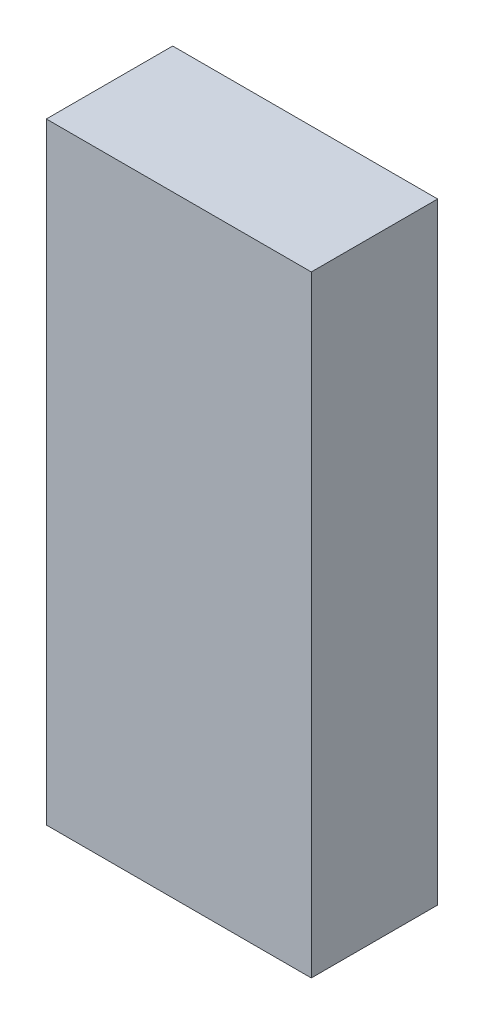
SolidWorks part; units mm, degrees
ref_plane "Front Plane" through (0, 0, 0) normal (0, 0, 1) x (1, 0, 0)
ref_plane "Top Plane" through (0, 0, 0) normal (0, 1, 0) x (1, 0, 0)
ref_plane "Right Plane" through (0, 0, 0) normal (1, 0, 0) x (0, 0, -1)
sketch "Sketch1" plane through (0, 0, 0) normal (0, 0, 1) x (1, 0, 0)
  line L0 (16.51, 38.1) -> (-16.51, -38.1) construction
  line L1 (-16.51, 38.1) -> (16.51, 38.1)
  line L2 (-16.51, 38.1) -> (-16.51, -38.1)
  line L3 (-16.51, -38.1) -> (16.51, -38.1)
  line L4 (16.51, 38.1) -> (16.51, -38.1)
  point P4 (0, 0)
  dimension "D1" = 76.2
  dimension "D2" = 33.02
extrude "Boss-Extrude1" add sketch "Sketch1" along normal mid plane 15.748 contours L1 L4 L3 L2
